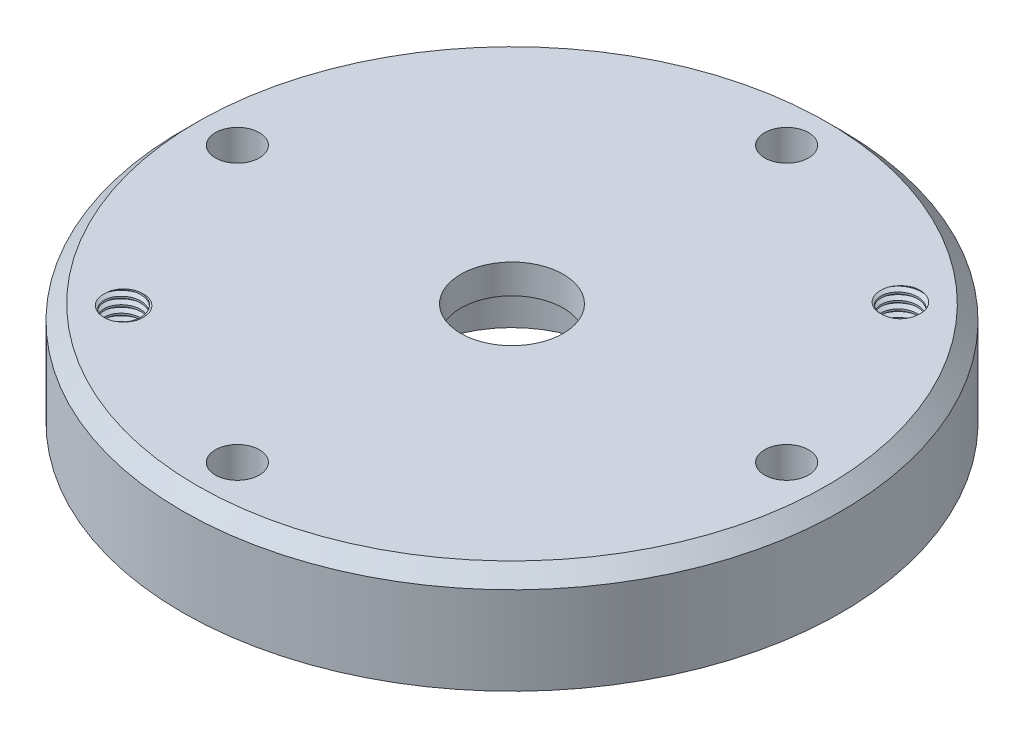
SolidWorks part; units mm, degrees
ref_plane "Front Plane" through (0, 0, 0) normal (0, 0, 1) x (1, 0, 0)
ref_plane "Top Plane" through (0, 0, 0) normal (0, 1, 0) x (1, 0, 0)
ref_plane "Right Plane" through (0, 0, 0) normal (1, 0, 0) x (0, 0, -1)
sketch "Sketch1" plane through (0, 0, 0) normal (0, 1, 0) x (1, 0, 0)
  circle A0 centre (0, 0) radius 22.5
  circle A1 centre (0, 0) radius 15.1
  dimension "D1" = 45
  dimension "D2" = 30.2
extrude "Boss-Extrude1" add sketch "Sketch1" along normal blind 7
sketch "Sketch2" plane through (0, 7, 0) normal (0, 1, 0) x (1, 0, 0)
  circle A0 centre (0, 0) radius 16.9947
  circle A1 centre (0, 0) radius 6.5
  dimension "D1" = 13
extrude "Boss-Extrude2" add sketch "Sketch2" against normal blind 6
sketch "Sketch3" plane through (0, 7, 0) normal (0, 1, 0) x (1, 0, 0)
  circle A0 centre (0, 0) radius 3.5
  circle A1 centre (0, 0) radius 13.2959
  dimension "D1" = 7
extrude "Boss-Extrude3" add sketch "Sketch3" against normal blind 2
sketch "Sketch4" plane through (0, 7, 0) normal (0, 1, 0) x (1, 0, 0)
  line L0 (-13.2583, -13.2583) -> (13.2583, 13.2583) construction
  line L1 (13.2583, 13.2583) -> (13.2583, -13.2583) construction
  circle A0 centre (0, 0) radius 18.75 construction
  circle A1 centre (0, 18.75) radius 1.5
  circle A2 centre (-18.75, 0) radius 1.5
  circle A3 centre (0, -18.75) radius 1.5
  circle A4 centre (18.75, 0) radius 1.5
  circle A5 centre (-13.2583, -13.2583) radius 1.25
  circle A6 centre (13.2583, 13.2583) radius 1.25
  dimension "D1" = 37.5
  dimension "D3" = 3
  dimension "D4" = 2.5
  dimension "D5" = 2.5
  dimension "D2" = 45
extrude "Cut-Extrude1" cut sketch "Sketch4" against normal blind 10
chamfer "Chamfer1" distance 1 angle 45 1 edges at (0, 7, 22.5)
thread "Thread1" pitch 0.5 method cut profile "Thread Profile2" start angle 0, offset 1, length 0, pitch 0.5, diameter 2.5
ref_plane "Plane2" through (-14.5083, 8, 13.2583) normal (0, 0, 1) x (-1, 0, 0)
sketch "Thread Profile2" plane through (-14.5083, 8, 13.2583) normal (0, 0, 1) x (-1, 0, 0)
  line L0 (0, 0) -> (0, 0.5) construction
  line L1 (0, 0) -> (0.2706, 0.1562)
  line L2 (0.2706, 0.1562) -> (0.2706, 0.2187)
  line L3 (0.2706, 0.2187) -> (0, 0.375)
  line L4 (0.2706, 0.1875) -> (0, 0.1875) construction
  line L11 (0, 0) -> (0, 0.375)
  point P2 (0, 0)
  dimension "Pitch" = 0.5
  dimension "Profile_Angle" = 60
  dimension "Profile_Land" = 0.0625
  dimension "Profile_Height" = 0.2706
pattern_circular "CirPattern1" count 2 over 360 about axis through (0, 7, 0) along (0, 1, 0) of "Thread1"
